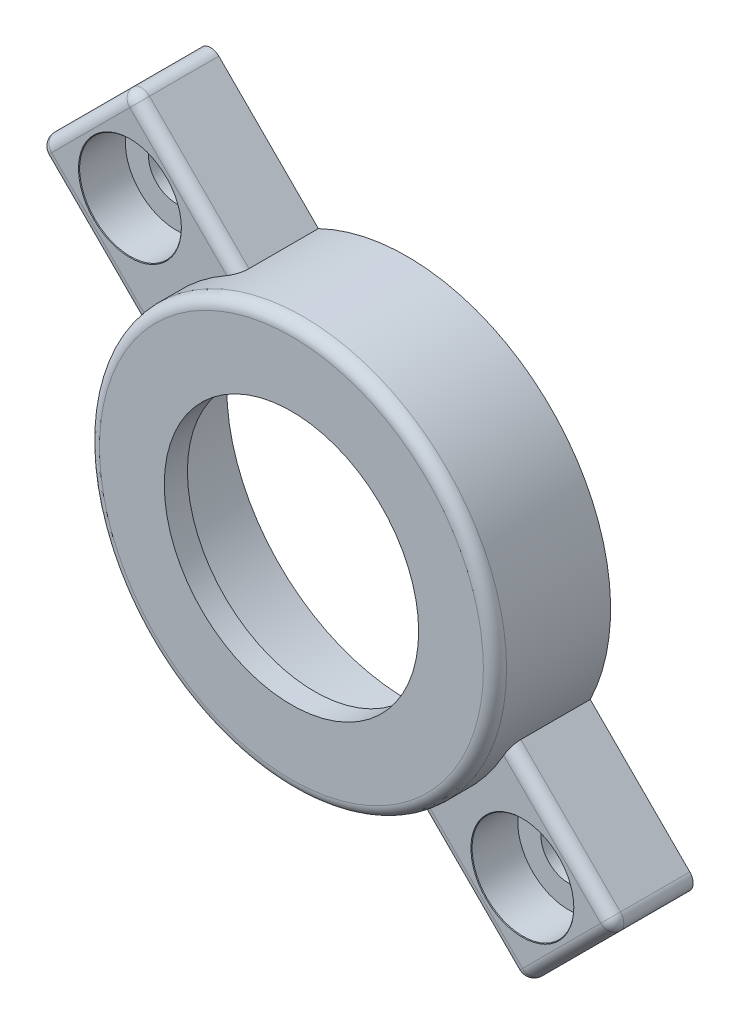
SolidWorks part; units mm, degrees
ref_plane "Front Plane" through (0, 0, 0) normal (0, 0, 1) x (1, 0, 0)
ref_plane "Top Plane" through (0, 0, 0) normal (0, 1, 0) x (1, 0, 0)
ref_plane "Right Plane" through (0, 0, 0) normal (1, 0, 0) x (0, 0, -1)
sketch "Sketch1" plane through (0, 0, 0) normal (0, 0, 1) x (1, 0, 0)
  line L0 (-8.485, 8.485) -> (8.485, -8.485)
  line L2 (8.4936, -12.5776) -> (3.8359, -7.92)
  line L3 (8.4936, -12.5776) -> (12.5776, -8.4936)
  line L5 (12.5776, -8.4936) -> (7.92, -3.8359)
  line L9 (-12.5776, 8.4936) -> (-7.92, 3.8359)
  line L10 (-8.4936, 12.5776) -> (-12.5776, 8.4936)
  line L11 (-8.4936, 12.5776) -> (-3.8359, 7.92)
  circle A0 centre (0, 0) radius 8.8
  point P17 (0, 0)
  point P19 (0, 0)
  point P20 (0, 0)
  dimension "D1" = 17.6
  dimension "D2" = 2
extrude "Boss-Extrude1" add sketch "Sketch1" along normal blind 5 contours A0 L0 | L0 A0 region at (2.6409, 2.6409, 0) region at (-2.6409, -2.6409, 0)
shell "Shell1" thickness 1 removed face at (8.8, 0, 0)
extrude "Boss-Extrude2" add sketch "Sketch1<4>" along normal blind 3.5 contours A0 L3 L2 | A0 region at (-7.272, 5.172, 0) region at (7.272, -5.172, 0)
sketch "Sketch1<4>" plane through (0, 0, 0) normal (0, 0, 1) x (1, 0, 0) same geometry as "Sketch1"
sketch "Sketch2" plane through (0, 0, 3.5) normal (0, 0, 1) x (1, 0, 0)
  line L12 (6.2264, 7.1669) -> (4.8122, 5.7526)
  line L13 (7.1669, 6.2264) -> (6.2264, 7.1669)
  line L14 (5.7526, 4.8122) -> (7.1669, 6.2264)
  line L15 (7.1669, -6.2264) -> (5.7526, -4.8122)
  line L16 (6.2264, -7.1669) -> (7.1669, -6.2264)
  line L17 (4.8122, -5.7526) -> (6.2264, -7.1669)
  line L18 (-6.2264, -7.1669) -> (-4.8122, -5.7526)
  line L19 (-7.1669, -6.2264) -> (-6.2264, -7.1669)
  line L20 (-5.7526, -4.8122) -> (-7.1669, -6.2264)
  line L21 (-7.1669, 6.2264) -> (-5.7526, 4.8122)
  line L22 (-6.2264, 7.1669) -> (-7.1669, 6.2264)
  line L23 (-4.8122, 5.7526) -> (-6.2264, 7.1669)
  line L24 (6.2264, 7.1669) -> (4.8122, 5.7526)
  line L25 (7.1669, 6.2264) -> (6.2264, 7.1669)
  line L26 (5.7526, 4.8122) -> (7.1669, 6.2264)
  line L27 (7.1669, -6.2264) -> (5.7526, -4.8122)
  line L28 (6.2264, -7.1669) -> (7.1669, -6.2264)
  line L29 (4.8122, -5.7526) -> (6.2264, -7.1669)
  line L30 (-6.2264, -7.1669) -> (-4.8122, -5.7526)
  line L31 (-7.1669, -6.2264) -> (-6.2264, -7.1669)
  line L32 (-5.7526, -4.8122) -> (-7.1669, -6.2264)
  line L33 (-7.1669, 6.2264) -> (-5.7526, 4.8122)
  line L34 (-6.2264, 7.1669) -> (-7.1669, 6.2264)
  line L35 (-4.8122, 5.7526) -> (-6.2264, 7.1669)
  circle A1 centre (12.375, 12.375) radius 0.6
  circle A2 centre (12.375, 12.375) radius 0.6
  circle A3 centre (12.375, -12.375) radius 0.6
  arc A4 (4.8122, 5.7526) -> (-4.8122, 5.7526) centre (0, 0) ccw
  arc A5 (5.7526, -4.8122) -> (5.7526, 4.8122) centre (0, 0) ccw
  arc A6 (-4.8122, -5.7526) -> (4.8122, -5.7526) centre (0, 0) ccw
  arc A7 (-5.7526, 4.8122) -> (-5.7526, -4.8122) centre (0, 0) ccw
  arc A8 (4.8122, 5.7526) -> (-4.8122, 5.7526) centre (0, 0) ccw
  arc A9 (5.7526, -4.8122) -> (5.7526, 4.8122) centre (0, 0) ccw
  arc A10 (-4.8122, -5.7526) -> (4.8122, -5.7526) centre (0, 0) ccw
  arc A11 (-5.7526, 4.8122) -> (-5.7526, -4.8122) centre (0, 0) ccw
  circle A12 centre (12.375, -12.375) radius 0.6
  circle A13 centre (8.485, 8.485) radius 1.2
  circle A14 centre (8.485, 8.485) radius 1.2
  circle A15 centre (-12.375, -12.375) radius 0.6
  circle A16 centre (-12.375, -12.375) radius 0.6
  circle A17 centre (8.485, -8.485) radius 1.2
  circle A18 centre (8.485, -8.485) radius 1.2
  circle A19 centre (-12.375, 12.375) radius 0.6
  circle A20 centre (-12.375, 12.375) radius 0.6
  circle A21 centre (-8.485, -8.485) radius 1.2
  circle A22 centre (-8.485, -8.485) radius 1.2
  circle A23 centre (-8.485, 8.485) radius 1.2
  circle A24 centre (-8.485, 8.485) radius 1.2
  circle A25 centre (-25.8094, 25.8094) radius 1.2
  circle A26 centre (-25.8094, 25.8094) radius 1.2
  circle A27 centre (-25.8094, -25.8094) radius 1.2
  circle A28 centre (-25.8094, -25.8094) radius 1.2
  circle A29 centre (25.8094, -25.8094) radius 1.2
  circle A30 centre (25.8094, -25.8094) radius 1.2
  circle A31 centre (25.8094, 25.8094) radius 1.2
  circle A32 centre (25.8094, 25.8094) radius 1.2
  point P34 (8.485, -8.485)
  point P43 (-8.485, 8.485)
  dimension "D1" = 0
  dimension "D2" = 0
  dimension "D3" = 0
  dimension "D4" = 0
  dimension "D5" = 0
  dimension "D6" = 0
  dimension "D7" = 0
  dimension "D8" = 0
  dimension "D9" = 0
  dimension "D10" = 0
  dimension "D11" = 0
  dimension "D12" = 0
  dimension "D13" = 0
hole_wizard "CBORE for M2 SHCS1" positions "Sketch2" profile "Sketch4" counterbore size "M2" standard "ANSI Metric" end condition through all
sketch "Sketch4" plane through (-8.485, 8.485, 3.5) normal (1, 0, 0) x (0, -1, 0)
  line L0 (0, 0) -> (0, 3.5)
  line L1 (0, 3.5) -> (1.2, 3.5)
  line L3 (1.2, 3.5) -> (1.2, 2)
  line L4 (2.2, 2) -> (1.2, 2)
  line L5 (2.2, 2) -> (2.2, 0.025)
  line L6 (2.2, 0.025) -> (2.225, 0)
  line L7 (2.225, 0) -> (0, 0)
  line L8 (-2.2, 0.025) -> (-2.225, 0) construction
  line L11 (0, -6.35) -> (0, 107.95) construction
  dimension "Thru Hole Dia." = 2.4
  dimension "Thru Hole Depth" = 3.5
  dimension "C'Bore Dia." = 4.4
  dimension "C'Bore Depth" = 2
  dimension "Near C'Sink Dia." = 4.45
  dimension "Near C'Sink Angle" = 90
fillet "Fillet1" radius 0.5 11 edges at (-8.4936, 12.5776, 1.75) (-6.1647, 10.2488, 3.5) (-10.5356, 10.5356, 3.5) (-12.5776, 8.4936, 1.75) (-10.2488, 6.1647, 3.5) (12.5776, -8.4936, 1.75) (10.2488, -6.1647, 3.5) (10.5356, -10.5356, 3.5) (8.4936, -12.5776, 1.75) (6.1647, -10.2488, 3.5) (8.8, 0, 5)
sketch "Sketch5" plane through (0, 0, 5) normal (0, 0, 1) x (1, 0, 0)
  circle A0 centre (0, 0) radius 5.5
  dimension "D1" = 11
extrude "Cut-Extrude1" cut sketch "Sketch5" against normal blind 10
